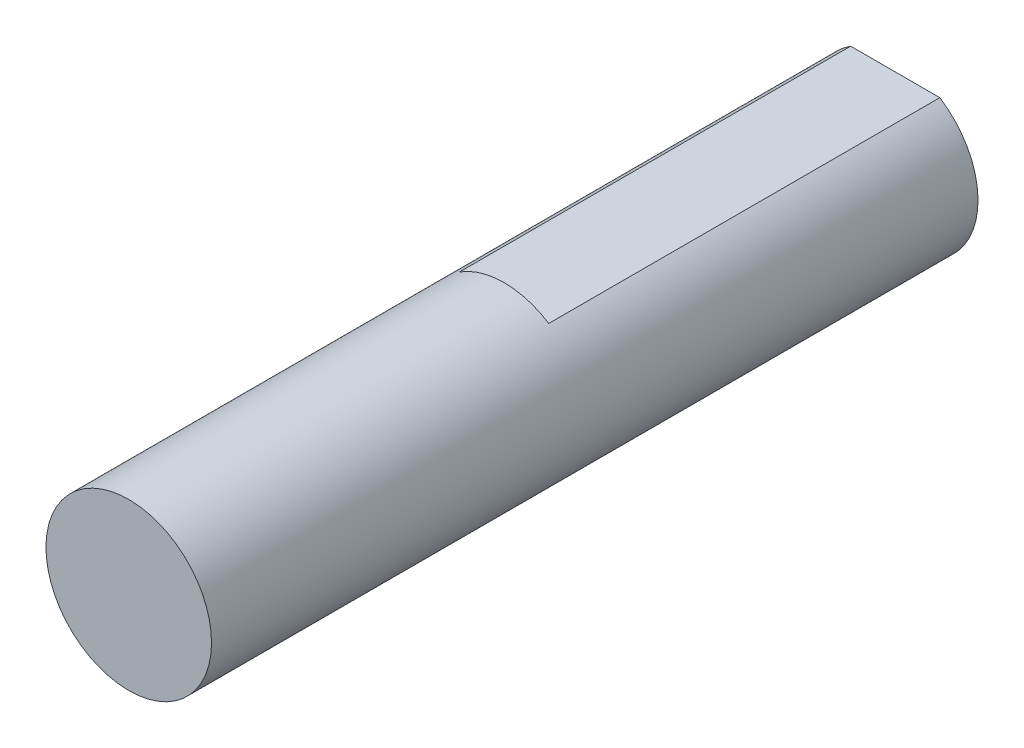
SolidWorks part; units mm, degrees
ref_plane "Front Plane" through (0, 0, 0) normal (0, 0, 1) x (1, 0, 0)
ref_plane "Top Plane" through (0, 0, 0) normal (0, 1, 0) x (1, 0, 0)
ref_plane "Right Plane" through (0, 0, 0) normal (1, 0, 0) x (0, 0, -1)
sketch "Sketch1" plane through (0, 0, 0) normal (0, 0, 1) x (1, 0, 0)
  line L0 (0, 5.7997) -> (0, 0) construction
  line L1 (0, 2.675) -> (-1.7103, 2.675)
  line L2 (0, 2.675) -> (1.7103, 2.675)
  line L3 (-2.0281, 3.175) -> (2.2806, 3.175) construction
  circle A0 centre (0, 0) radius 3.175
  dimension "D1" = 6.35
  dimension "D2" = 0.5
extrude "Boss-Extrude1" add sketch "Sketch1" along normal blind 29.4 contours L1 A0 L2 | L2 A0 L1 region at (0, -0.1093, 0) region at (0, 2.8764, 0)
extrude "Cut-Extrude1" cut sketch "Sketch1<3>" along normal blind 15 contours L2 A0 L1 region at (0, 2.8764, 0)
sketch "Sketch1<3>" plane through (0, 0, 0) normal (0, 0, 1) x (1, 0, 0) same geometry as "Sketch1"
